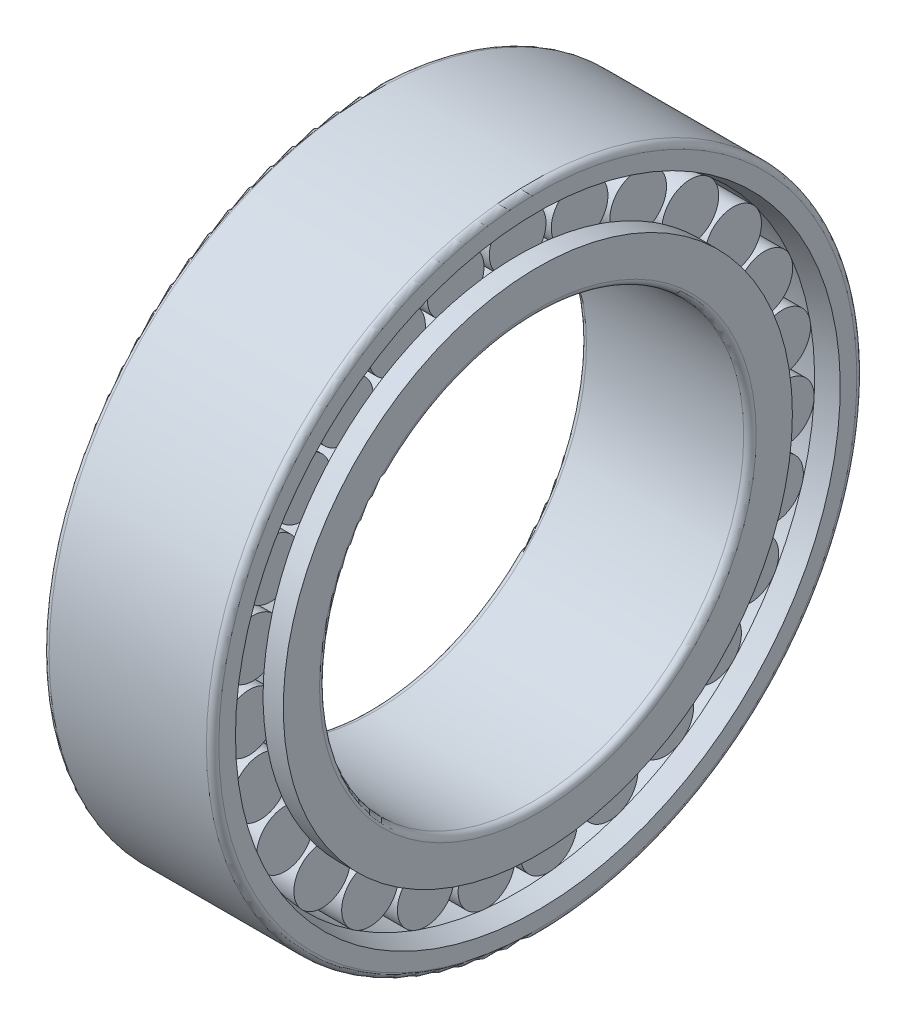
SolidWorks part; units mm, degrees
material "AISI 304"
ref_plane "前视" through (0, 0, 0) normal (0, 0, 1) x (1, 0, 0)
ref_plane "上视" through (0, 0, 0) normal (0, 1, 0) x (1, 0, 0)
ref_plane "右视" through (0, 0, 0) normal (1, 0, 0) x (0, 0, -1)
sketch "尺寸草图" plane through (0, 0, 0) normal (0, 0, 1) x (1, 0, 0)
  line L0 (0, 0) -> (115, 0)
  line L1 (0, 0) -> (0, 105)
  point P3 (75, 0)
  point P4 (30, 0)
  point P5 (1.1, 0)
  dimension "DD" = 115
  dimension "d" = 75
  dimension "B" = 30
  dimension "r" = 1.1
  dimension "Ew" = 105
sketch "草图1" plane through (0, 0, 0) normal (0, 0, 1) x (1, 0, 0)
  line L0 (0, 0) -> (0, 110.1282) construction
  line L1 (0, 0) -> (226.5796, 0) construction
  line L2 (1.1, 57.5) -> (28.9, 57.5)
  line L3 (30, 38.6) -> (30, 45) construction
  line L4 (1.1, 37.5) -> (28.9, 37.5) construction
  line L5 (0, 56.4) -> (0, 53.457)
  line L6 (-94.0488, 47.5) -> (162.4539, 47.5) construction
  line L7 (3.5714, 52.5) -> (26.4286, 52.5)
  line L8 (3.5714, 42.5) -> (12.1429, 42.5) construction
  line L9 (12.1429, 52.5) -> (12.1429, 42.5) construction
  line L10 (17.8571, 42.5) -> (17.8571, 52.5) construction
  line L11 (26.4286, 42.5) -> (26.4286, 52.5) construction
  line L12 (3.5714, 52.5) -> (3.5714, 42.5) construction
  line L13 (15, 57.5) -> (15, 37.5) construction
  line L14 (0, 45) -> (0, 38.6) construction
  line L15 (30, 53.457) -> (30, 56.4)
  line L16 (0, 45) -> (3.5714, 45) construction
  line L17 (12.1429, 45) -> (17.8571, 45) construction
  line L18 (26.4286, 45) -> (30, 45) construction
  line L19 (17.8571, 42.5) -> (26.4286, 42.5) construction
  line L20 (0, 53.457) -> (3.5714, 52.5)
  line L21 (26.4286, 52.5) -> (30, 53.457)
  arc A0 (1.1, 57.5) -> (0, 56.4) centre (1.1, 56.4) ccw
  arc A1 (28.9, 57.5) -> (30, 56.4) centre (28.9, 56.4) cw
  arc A2 (1.1, 37.5) -> (0, 38.6) centre (1.1, 38.6) cw construction
  arc A3 (28.9, 37.5) -> (30, 38.6) centre (28.9, 38.6) ccw construction
  point P15 (0, 52.5)
  point P16 (30, 52.5)
  point P30 (0, 57.5)
  point P33 (30, 57.5)
  dimension "D8" = 1.1
  dimension "D4" = 22.8571
  dimension "D3" = 115
  dimension "D5" = 5.7143
  dimension "D6" = 105
  dimension "D7" = 10
  dimension "D2" = 30
  dimension "D9" = 3.5714
  dimension "D10" = 15
  dimension "D11" = 3.5714
  dimension "D12" = 15
  dimension "D13" = 37.5
  dimension "D14" = 2.5
revolve "基体-旋转" add sketch "草图1" angle 360 about L1
sketch "草图4" plane through (0, 0, 0) normal (0, 0, 1) x (1, 0, 0)
  line L0 (3.5714, 47.5) -> (12.1429, 47.5)
  line L1 (3.5714, 52.5) -> (26.4286, 52.5) construction
  line L2 (12.1429, 52.5) -> (12.1429, 42.5) construction
  line L3 (-94.0488, 47.5) -> (162.4539, 47.5) construction
  line L4 (3.5714, 52.5) -> (3.5714, 42.5) construction
  line L5 (3.5714, 52.501) -> (12.1429, 52.501)
  line L6 (3.5714, 52.5) -> (12.1429, 52.5) construction
  line L7 (12.1429, 52.501) -> (12.1429, 47.5)
  line L8 (-94.0488, 47.5) -> (162.4539, 47.5) construction
  line L9 (3.5714, 52.501) -> (3.5714, 47.5)
  line L10 (0, 0) -> (30, 0) construction
  line L11 (30, -56.4) -> (30, 56.4) construction
  dimension "D2" = 47.5
  dimension "D3" = 5.001
  dimension "D1" = 0.001
revolve "凸台-旋转1" add sketch "草图4" angle 360 about L8
sketch "草图5" plane through (0, 0, 0) normal (0, 0, 1) x (1, 0, 0)
  line L0 (3.5714, 52.5) -> (26.4286, 52.5) construction
  line L1 (-94.0488, 47.5) -> (162.4539, 47.5) construction
  line L2 (26.4286, 42.5) -> (26.4286, 52.5) construction
  line L3 (17.8571, 42.5) -> (17.8571, 52.5) construction
  line L4 (17.8571, 52.5) -> (26.4286, 52.5) construction
  line L5 (-94.0488, 47.5) -> (162.4539, 47.5) construction
  line L6 (26.4286, 47.5) -> (26.4286, 52.51)
  line L7 (17.8571, 47.5) -> (17.8571, 52.51)
  line L8 (17.8571, 52.51) -> (26.4286, 52.51)
  line L9 (17.8571, 47.5) -> (26.4286, 47.5)
  dimension "D1" = 0.01
revolve "凸台-旋转2" add sketch "草图5" angle 360 about L5
sketch "草图2" plane through (0, 0, 0) normal (0, 0, 1) x (1, 0, 0)
  line L1 (12.1429, 52.5) -> (12.1429, 42.5) construction
  line L3 (12.1429, 45) -> (17.8571, 45) construction
  line L4 (1.1, 37.5) -> (28.9, 37.5) construction
  line L6 (17.8571, 42.5) -> (26.4286, 42.5) construction
  line L9 (3.5714, 42.5) -> (12.1429, 42.5) construction
  line L10 (26.4286, 42.5) -> (26.4286, 45)
  line L11 (12.1429, 45) -> (12.1429, 42.5)
  line L12 (26.4286, 45) -> (30, 45)
  line L13 (12.1429, 45) -> (17.8571, 45)
  line L14 (1.1, 37.5) -> (28.9, 37.5)
  line L15 (30, 38.6) -> (30, 45)
  line L16 (17.8571, 42.5) -> (26.4286, 42.5)
  line L17 (0, 45) -> (0, 38.6)
  line L18 (0, 45) -> (3.5714, 45)
  line L19 (3.5714, 42.5) -> (12.1429, 42.5)
  line L20 (17.8571, 42.5) -> (17.8571, 52.5) construction
  line L22 (17.8571, 42.5) -> (17.8571, 45)
  line L23 (3.5714, 45) -> (3.5714, 42.5)
  line L24 (3.5714, 52.5) -> (3.5714, 42.5) construction
  line L25 (0, 0) -> (0, 110.1282) construction
  line L26 (0, 0) -> (-135.6746, 0) construction
  line L27 (26.4286, 42.5) -> (26.4286, 52.5) construction
  arc A0 (28.9, 37.5) -> (30, 38.6) centre (28.9, 38.6) ccw construction
  arc A1 (0, 38.6) -> (1.1, 37.5) centre (1.1, 38.6) ccw construction
  arc A2 (28.9, 37.5) -> (30, 38.6) centre (28.9, 38.6) ccw
  arc A3 (0, 38.6) -> (1.1, 37.5) centre (1.1, 38.6) ccw
revolve "凸台-旋转3" add sketch "草图2" angle 360 about L26
ref_axis "基准轴1" through (-5.3, 0, 0) along (1, 0, 0)
pattern_circular "阵列(圆周)2" count 27 over 360 about axis through (-5.3, 0, 0) along (1, 0, 0) of "凸台-旋转1", "凸台-旋转2"
